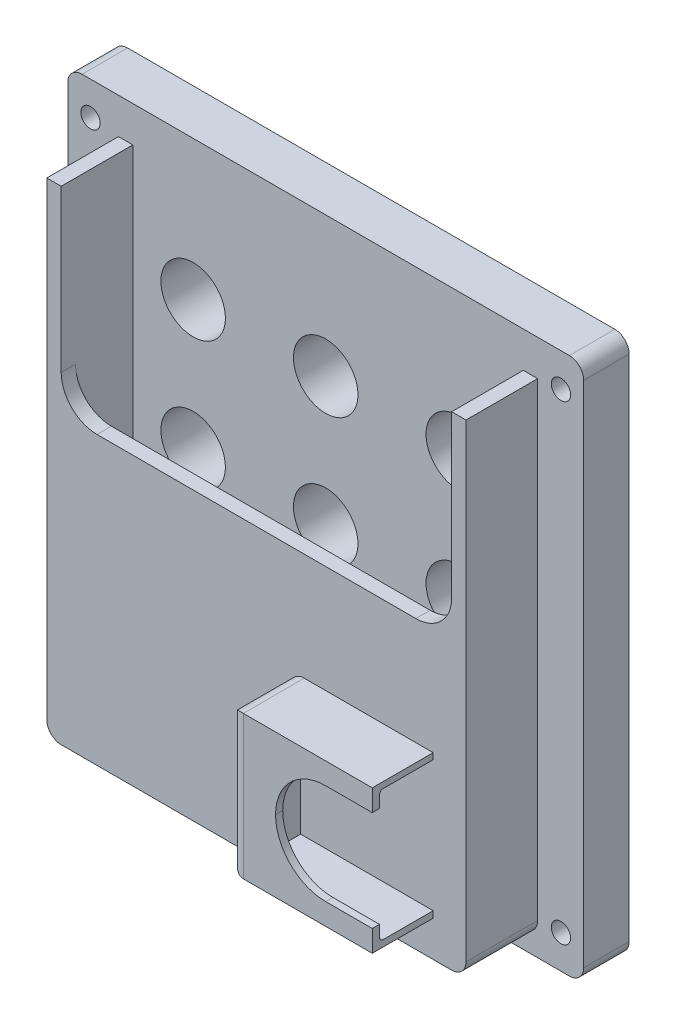
SolidWorks part; units mm, degrees
ref_plane "Front Plane" through (0, 0, 0) normal (0, 0, 1) x (1, 0, 0)
ref_plane "Top Plane" through (0, 0, 0) normal (0, 1, 0) x (1, 0, 0)
ref_plane "Right Plane" through (0, 0, 0) normal (1, 0, 0) x (0, 0, -1)
sketch "Sketch1" plane through (0, 0, 0) normal (0, 0, 1) x (1, 0, 0)
  line L0 (0, 0) -> (0, 37.5) construction
  line L1 (-36, 37.5) -> (36, 37.5)
  line L2 (-36, 37.5) -> (-36, -37.5)
  line L3 (-36, -37.5) -> (36, -37.5)
  line L4 (36, 37.5) -> (36, -37.5)
  line L5 (-36, 37.5) -> (36, -37.5) construction
  line L6 (-36, -37.5) -> (36, 37.5) construction
  line L7 (0, 0) -> (36, 0) construction
  circle A0 centre (-32.83, 32.83) radius 1.35
  circle A1 centre (-32.83, -32.83) radius 1.35
  circle A2 centre (32.83, 32.83) radius 1.35
  circle A3 centre (32.83, -32.83) radius 1.35
  point P0 (0, 0)
  dimension "D5" = 2.7
  dimension "D1" = 72
  dimension "D2" = 75
  dimension "D3" = 65.66
  dimension "D4" = 65.66
extrude "Boss-Extrude1" add sketch "Sketch1" along normal blind 6.35
sketch "Sketch2" plane through (0, 0, 6.35) normal (0, 0, 1) x (1, 0, 0)
  line L0 (0, 0) -> (0, 37.5) construction
  line L1 (36, 37.5) -> (-36, 37.5) construction
  line L2 (0, 0) -> (36, 0) construction
  line L3 (36, -37.5) -> (36, 37.5) construction
  line L4 (-32.83, 32.83) -> (-32.83, -32.83) construction
  line L5 (-28.92, 32.5) -> (-26.92, 32.5)
  line L6 (-28.92, 32.5) -> (-28.92, -32.5)
  line L7 (-28.92, -32.5) -> (-26.92, -32.5)
  line L8 (-26.92, 32.5) -> (-26.92, -32.5)
  line L9 (27.58, 32.5) -> (29.58, 32.5)
  line L10 (27.58, 32.5) -> (27.58, -32.5)
  line L11 (27.58, -32.5) -> (29.58, -32.5)
  line L12 (29.58, 32.5) -> (29.58, -32.5)
  line L13 (32.83, -32.83) -> (32.83, 32.83) construction
  line L15 (-28.92, -32.5) -> (29.58, -32.5)
  line L16 (-28.92, -32.5) -> (-28.92, -35)
  line L17 (-28.92, -35) -> (29.58, -35)
  line L18 (29.58, -32.5) -> (29.58, -35)
  dimension "D1" = 2.5
  dimension "D2" = 3.25
  dimension "D3" = 2
  dimension "D4" = 2
  dimension "D6" = 65
  dimension "D7" = 58.5
extrude "Boss-Extrude2" add sketch "Sketch2" along normal blind 10 contours L12 L9 L10 L11 | L18 L11 L15 L7 L16 L17 | L6 L5 L8 L7 region at (0.33, -33.75, 6.35) region at (28.58, 0, 6.35)
sketch "Sketch3" plane through (0, 0, 16.35) normal (0, 0, 1) x (1, 0, 0)
  line L0 (29.58, 32.5) -> (29.58, -35) construction
  line L1 (-28.92, -35) -> (29.58, -35)
  line L2 (-28.92, -35) -> (-28.92, 5)
  line L3 (-28.92, 5) -> (29.58, 5)
  line L4 (29.58, -35) -> (29.58, 5)
  dimension "D1" = 40
extrude "Boss-Extrude3" add sketch "Sketch3" against normal blind 2
fillet "Fillet1" radius 5 2 edges at (-26.92, 5, 15.35) (27.58, 5, 15.35)
sketch "Sketch4" plane through (0, 0, 16.35) normal (0, 0, 1) x (1, 0, 0)
  line L0 (0, 0) -> (0, 37.5) construction
  line L1 (5, -10) -> (25, -10)
  line L2 (5, -10) -> (5, -30)
  line L3 (5, -30) -> (25, -30)
  line L4 (25, -10) -> (25, -30)
  line L5 (36, 37.5) -> (-36, 37.5) construction
  line L6 (0, 0) -> (36, 0) construction
  line L7 (36, -37.5) -> (36, 37.5) construction
  dimension "D1" = 10
  dimension "D2" = 5
  dimension "D3" = 20
  dimension "D4" = 20
extrude "Boss-Extrude4" add sketch "Sketch4" along normal blind 8.5
sketch "Sketch5" plane through (25, 0, 0) normal (1, 0, 0) x (0, 0, -1)
  line L0 (-16.35, -30) -> (-16.35, -10) construction
  line L1 (-16.35, -29.1) -> (-23.85, -29.1)
  line L2 (-16.35, -29.1) -> (-16.35, -10.85)
  line L3 (-16.35, -10.85) -> (-23.85, -10.85)
  line L4 (-23.85, -29.1) -> (-23.85, -10.85)
  line L5 (-24.85, -30) -> (-16.35, -30) construction
  dimension "D1" = 18.25
  dimension "D2" = 0.9
  dimension "D3" = 7.5
extrude "Cut-Extrude1" cut sketch "Sketch5" against normal blind 18.5
fillet "Fillet2" radius 0.5 2 edges at (15.75, -29.1, 23.85) (15.75, -10.85, 23.85)
fillet "Fillet3" radius 2 6 edges at (-36, 37.5, 3.175) (36, 37.5, 3.175) (29.58, -35, 11.35) (36, -37.5, 3.175) (-36, -37.5, 3.175) (-28.92, -35, 11.35)
fillet "Fillet4" radius 2 3 edges at (5, -20, 24.85) (5, -10, 20.6) (5, -30, 20.6)
sketch "Sketch6" plane through (0, 0, 24.85) normal (0, 0, 1) x (1, 0, 0)
  line L0 (25, -30) -> (25, -10) construction
  line L1 (25, -27) -> (11.5, -27)
  line L2 (25, -27) -> (25, -13)
  line L3 (25, -13) -> (11.5, -13)
  line L4 (11.5, -27) -> (11.5, -13)
  line L5 (7, -20) -> (5, -20) construction
  line L6 (7, -10) -> (7, -30) construction
  line L7 (5, -12) -> (5, -28) construction
  point P12 (0, 0)
  dimension "D1" = 14
  dimension "D2" = 13.5
extrude "Cut-Extrude2" cut sketch "Sketch6" against normal up to next
fillet "Fillet5" radius 7 2 edges at (11.5, -27, 24.35) (11.5, -13, 24.35)
sketch "Sketch7" plane through (0, 0, 0) normal (0, 0, -1) x (-1, 0, 0)
  line L0 (0, 37.5) -> (0, -37.5) construction
  line L1 (-34, 37.5) -> (34, 37.5) construction
  line L2 (34, -37.5) -> (-34, -37.5) construction
  line L3 (-36, 0) -> (36, 0) construction
  line L4 (-36, -35.5) -> (-36, 35.5) construction
  line L5 (36, 35.5) -> (36, -35.5) construction
  circle A0 centre (-18.5, 18) radius 4.5
  circle A1 centre (0, 18) radius 4.5
  circle A2 centre (18.5, 18) radius 4.5
  circle A3 centre (-18.5, 0) radius 4.5
  circle A4 centre (0, 0) radius 4.5
  circle A5 centre (18.5, 0) radius 4.5
  circle A6 centre (0, -18) radius 4.5
  circle A7 centre (18.5, -18) radius 4.5
  circle A8 centre (-18.5, -18) radius 4.5
  point P31 (0, 0)
  point P32 (0, 0)
  point P33 (0, 0)
  point P34 (0, 0)
  dimension "D1" = 9
  dimension "D2" = 18.5
  dimension "D3" = 18.5
  dimension "D4" = 18
  dimension "D5" = 18
extrude "Cut-Extrude3" cut sketch "Sketch7" against normal up to next
